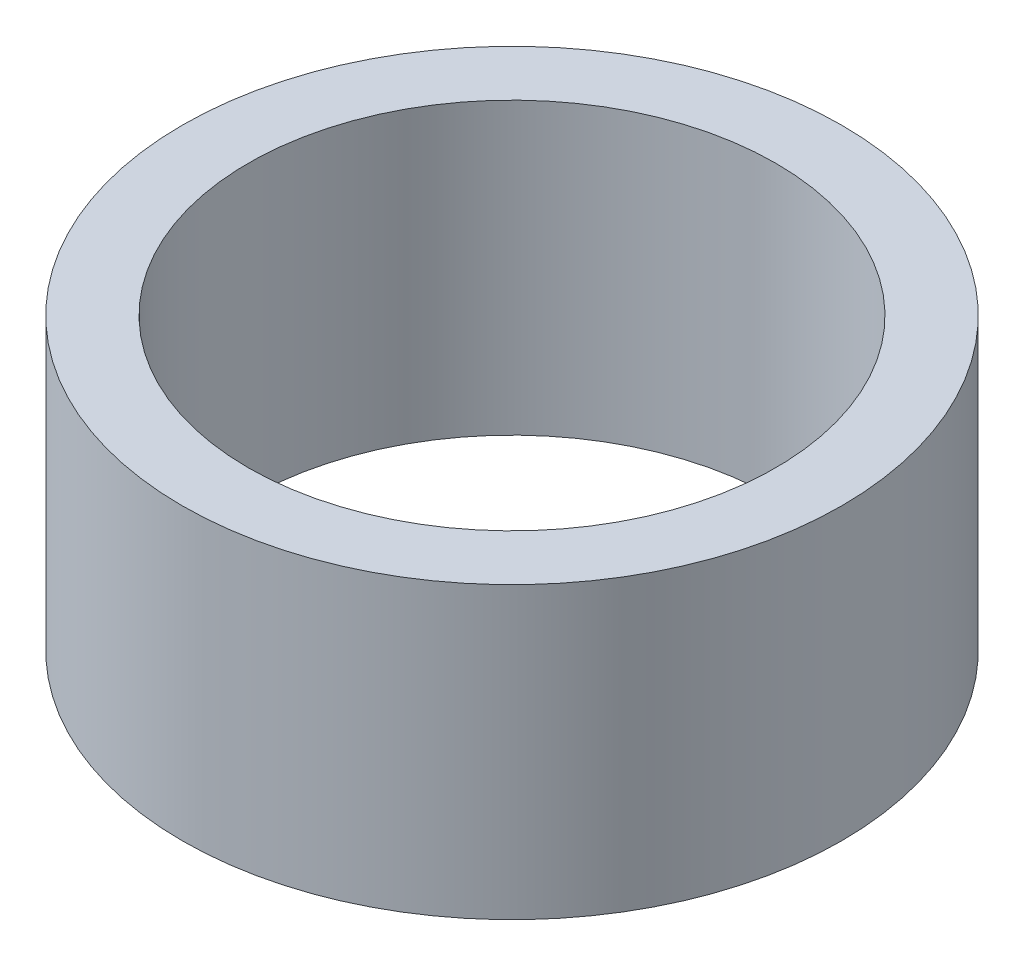
SolidWorks part; units mm, degrees
material "PC High Viscosity"
ref_plane "Front Plane" through (0, 0, 0) normal (0, 0, 1) x (1, 0, 0)
ref_plane "Top Plane" through (0, 0, 0) normal (0, 1, 0) x (1, 0, 0)
ref_plane "Right Plane" through (0, 0, 0) normal (1, 0, 0) x (0, 0, -1)
ref_axis "Axis1" through (0, 0.3, 0) along (0, -1, 0)
sketch "Sketch1" plane through (0, 0, 0) normal (0, 1, 0) x (1, 0, 0)
  circle A0 centre (0, 0) radius 5
  circle A1 centre (0, 0) radius 4
  dimension "D1" = 1
  dimension "D2" = 10
  dimension "D3" = 8
extrude "Boss-Extrude1" add sketch "Sketch1" against normal blind 4.4
